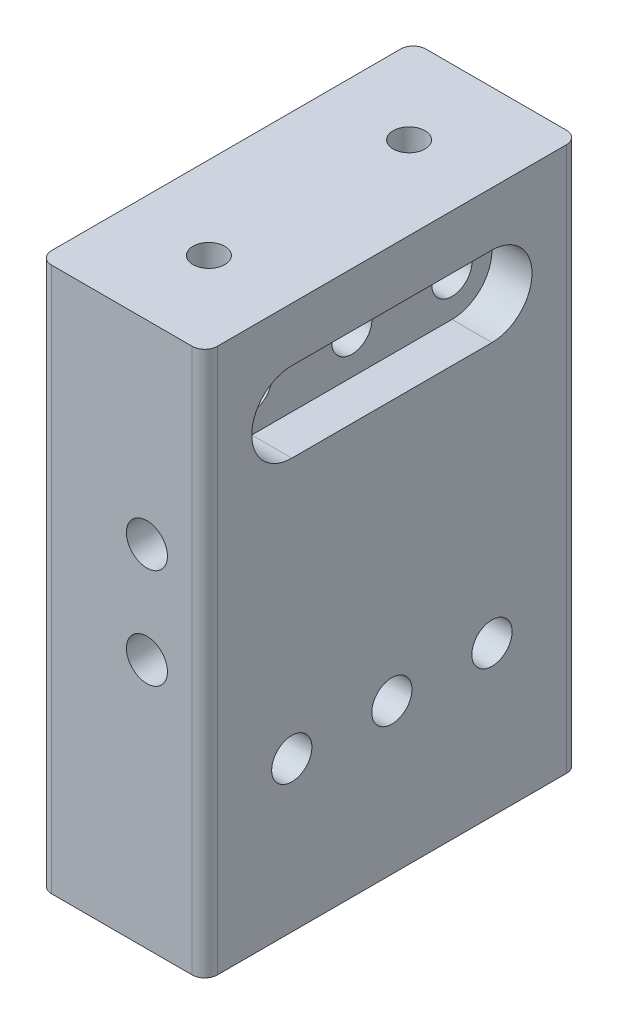
SolidWorks part; units mm, degrees
material "6061-T6 (SS)"
ref_plane "Front Plane" through (0, 0, 0) normal (0, 0, 1) x (1, 0, 0)
ref_plane "Top Plane" through (0, 0, 0) normal (0, 1, 0) x (1, 0, 0)
ref_plane "Right Plane" through (0, 0, 0) normal (1, 0, 0) x (0, 0, -1)
sketch "Sketch1" plane through (0, 0, 0) normal (0, 1, 0) x (1, 0, 0)
  line L1 (-10.5156, -23.7427) -> (10.5156, -23.7427)
  line L2 (-10.5156, -23.7427) -> (-10.5156, 23.7426)
  line L3 (-10.5156, 23.7426) -> (10.5156, 23.7426)
  line L4 (10.5156, -23.7427) -> (10.5156, 23.7426)
  line L5 (-10.5156, -23.7427) -> (10.5156, 23.7426) construction
  line L6 (-10.5156, 23.7426) -> (10.5156, -23.7427) construction
  point P0 (0, 0)
  dimension "D1" = 21.0312
  dimension "D2" = 47.4853
extrude "Boss-Extrude1" add sketch "Sketch1" along normal mid plane 63.5
sketch "Sketch2" plane through (0, 0, 23.7427) normal (0, 0, 1) x (1, 0, 0)
  line L5 (-10.5156, 31.75) -> (10.5156, 31.75) construction
  circle A1 centre (3.175, 0) radius 2.6035
  circle A2 centre (3.175, 12.7) radius 2.6035
  dimension "D3" = 19.05
  dimension "D1" = 7.3406
  dimension "D2" = 5.207
  dimension "D4" = 12.7
extrude "Cut-Extrude1" cut sketch "Sketch2" against normal through all
sketch "Sketch4" plane through (10.5156, 0, 0) normal (1, 0, 0) x (0, 0, -1)
  line L0 (-23.7427, 31.75) -> (23.7426, 31.75) construction
  circle A0 centre (-12.7, 25.4) radius 2.5527
  circle A1 centre (12.7, 25.4) radius 2.5527
  circle A2 centre (0, 25.4) radius 2.5527
  dimension "D5" = 5.1054
  dimension "D1" = 6.35
  dimension "D3" = 12.7
  dimension "D4" = 12.7
extrude "Cut-Extrude3" cut sketch "Sketch4" against normal through all
fillet "Fillet1" radius 1.5875 4 edges at (10.5156, 0, 23.7427) (-10.5156, 0, 23.7427) (-10.5156, 0, -23.7426) (10.5156, 0, -23.7426)
sketch "Sketch7" plane through (10.5156, 0, 0) normal (1, 0, 0) x (0, 0, -1)
  line L0 (-12.7, 25.4) -> (12.7, 25.4) construction
  line L1 (-12.7, 30.48) -> (12.7, 30.48)
  line L2 (-12.7, 20.32) -> (12.7, 20.32)
  arc A0 (-12.7, 30.48) -> (-12.7, 20.32) centre (-12.7, 25.4) ccw
  arc A1 (12.7, 20.32) -> (12.7, 30.48) centre (12.7, 25.4) ccw
  point P4 (0, 25.4)
  dimension "D1" = 5.08
extrude "Cut-Extrude5" cut sketch "Sketch7" against normal blind 5.08
sketch "Sketch8" plane through (0, 31.75, 0) normal (0, 1, 0) x (1, 0, 0)
  line L4 (-8.9281, -23.7427) -> (8.9281, -23.7427)
  line L5 (10.5156, -22.1552) -> (10.5156, 22.1551)
  line L6 (8.9281, 23.7426) -> (-8.9281, 23.7426)
  line L7 (-10.5156, 22.1551) -> (-10.5156, -22.1552)
  line L8 (-8.9281, -23.7427) -> (8.9281, -23.7427)
  line L9 (10.5156, -22.1552) -> (10.5156, 22.1551)
  line L10 (8.9281, 23.7426) -> (-8.9281, 23.7426)
  line L11 (-10.5156, 22.1551) -> (-10.5156, -22.1552)
  arc A4 (8.9281, -23.7427) -> (10.5156, -22.1552) centre (8.9281, -22.1552) ccw
  arc A5 (10.5156, 22.1551) -> (8.9281, 23.7426) centre (8.9281, 22.1551) ccw
  arc A6 (-8.9281, 23.7426) -> (-10.5156, 22.1551) centre (-8.9281, 22.1551) ccw
  arc A7 (-8.9281, 23.7426) -> (-10.5156, 22.1551) centre (-8.9281, 22.1551) ccw
  arc A8 (8.9281, -23.7427) -> (10.5156, -22.1552) centre (8.9281, -22.1552) ccw
  arc A9 (10.5156, 22.1551) -> (8.9281, 23.7426) centre (8.9281, 22.1551) ccw
  arc A10 (-10.5156, -22.1552) -> (-8.9281, -23.7427) centre (-8.9281, -22.1552) ccw
  arc A11 (-10.5156, -22.1552) -> (-8.9281, -23.7427) centre (-8.9281, -22.1552) ccw
  dimension "D1" = 0
extrude "Boss-Extrude2" add sketch "Sketch8" along normal blind 5.588
sketch "Sketch9" plane through (0, 37.338, 0) normal (0, 1, 0) x (1, 0, 0)
  line L0 (-10.5156, 0) -> (10.5156, 0) construction
  line L1 (-10.5156, 22.1551) -> (-10.5156, -22.1552) construction
  line L2 (10.5156, -22.1552) -> (10.5156, 22.1551) construction
  circle A0 centre (0, 12.7) radius 2.0193
  circle A2 centre (0, -12.7) radius 2.0193
  dimension "D2" = 4.0386
  dimension "D1" = 12.7
  dimension "D3" = 10.5156
extrude "Cut-Extrude6" cut sketch "Sketch9" against normal blind 5.08
sketch "Sketch10" plane through (-10.5156, 0, 0) normal (-1, 0, 0) x (0, 0, 1)
  line L1 (-22.1551, 37.338) -> (22.1552, 37.338) construction
  circle A0 centre (-12.7, -12.7) radius 2.5527
  circle A1 centre (0, -12.7) radius 2.5527
  circle A2 centre (12.7, -12.7) radius 2.5527
  dimension "D1" = 5.1054
  dimension "D2" = 50.038
  dimension "D3" = 12.7
  dimension "D4" = 12.7
extrude "Cut-Extrude7" cut sketch "Sketch10" against normal through all
